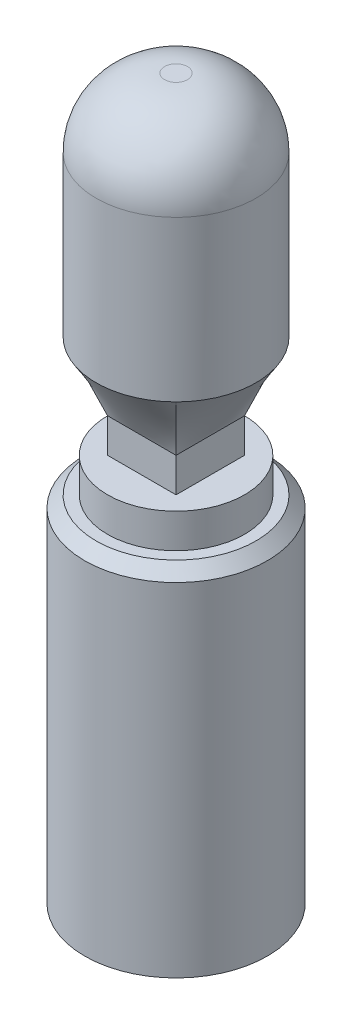
SolidWorks part; units mm, degrees
ref_plane "Front" through (0, 0, 0) normal (0, 0, 1) x (1, 0, 0)
ref_plane "Top" through (0, 0, 0) normal (0, 1, 0) x (1, 0, 0)
ref_plane "Right" through (0, 0, 0) normal (1, 0, 0) x (0, 0, -1)
sketch "Sketch1" plane through (0, 0, 0) normal (0, 1, 0) x (1, 0, 0)
  circle A0 centre (0, 0) radius 8
  dimension "D1" = 16
extrude "Boss-Extrude1" add sketch "Sketch1" along normal blind 30
sketch "Sketch2" plane through (0, 30, 0) normal (0, 1, 0) x (1, 0, 0)
  circle A1 centre (0, 0) radius 8
  circle A2 centre (0, 0) radius 8
  dimension "D1" = 0
extrude "Boss-Extrude2" add sketch "Sketch2" along normal blind 1 draft 45
sketch "Sketch3" plane through (0, 31, 0) normal (0, 1, 0) x (1, 0, 0)
  circle A0 centre (0, 0) radius 6
  dimension "D1" = 12
extrude "Boss-Extrude3" add sketch "Sketch3" along normal blind 3
sketch "Sketch4" plane through (0, 34, 0) normal (0, 1, 0) x (1, 0, 0)
  line L1 (-3, -3) -> (3, -3)
  line L2 (-3, -3) -> (-3, 3)
  line L3 (-3, 3) -> (3, 3)
  line L4 (3, -3) -> (3, 3)
  line L5 (-3, -3) -> (3, 3) construction
  line L6 (-3, 3) -> (3, -3) construction
  point P0 (0, 0)
  dimension "D1" = 6
extrude "Boss-Extrude4" add sketch "Sketch4" along normal blind 3
ref_plane "Plane1" through (0, 43, 0) normal (0, 1, 0) x (1, 0, 0)
sketch "Sketch5" plane through (0, 37, 0) normal (0, 1, 0) x (1, 0, 0)
  line L4 (3, -3) -> (3, 3)
  line L5 (3, 3) -> (-3, 3)
  line L6 (-3, 3) -> (-3, -3)
  line L7 (-3, -3) -> (3, -3)
  line L8 (3, -3) -> (3, 3)
  line L9 (3, 3) -> (-3, 3)
  line L10 (-3, 3) -> (-3, -3)
  line L11 (-3, -3) -> (3, -3)
  dimension "D1" = 0
sketch "Sketch6" plane through (0, 43, 0) normal (0, 1, 0) x (1, 0, 0)
  circle A0 centre (0, 0) radius 7
  dimension "D1" = 14
loft "Loft1" add profiles "Sketch6", "Sketch5"
sketch "Sketch7" plane through (0, 43, 0) normal (0, 1, 0) x (1, 0, 0)
  arc A4 (4.9497, -4.9497) -> (4.9497, 4.9497) centre (0, 0) ccw
  arc A5 (4.9497, 4.9497) -> (-4.9497, 4.9497) centre (0, 0) ccw
  arc A6 (-4.9497, 4.9497) -> (-4.9497, -4.9497) centre (0, 0) ccw
  arc A7 (-4.9497, -4.9497) -> (4.9497, -4.9497) centre (0, 0) ccw
  arc A8 (4.9497, -4.9497) -> (4.9497, 4.9497) centre (0, 0) ccw
  arc A9 (4.9497, 4.9497) -> (-4.9497, 4.9497) centre (0, 0) ccw
  arc A10 (-4.9497, 4.9497) -> (-4.9497, -4.9497) centre (0, 0) ccw
  arc A11 (-4.9497, -4.9497) -> (4.9497, -4.9497) centre (0, 0) ccw
  dimension "D1" = 0
extrude "Boss-Extrude5" add sketch "Sketch7" along normal blind 20
fillet "Fillet1" radius 6 1 edges at (0, 63, 7)
sketch "Sketch9" plane through (0, 0, 0) normal (0, -1, 0) x (1, 0, 0)
  circle A0 centre (0, 0) radius 2.05
  dimension "D1" = 4.1
extrude "Cut-Extrude1" cut sketch "Sketch9" against normal blind 6
